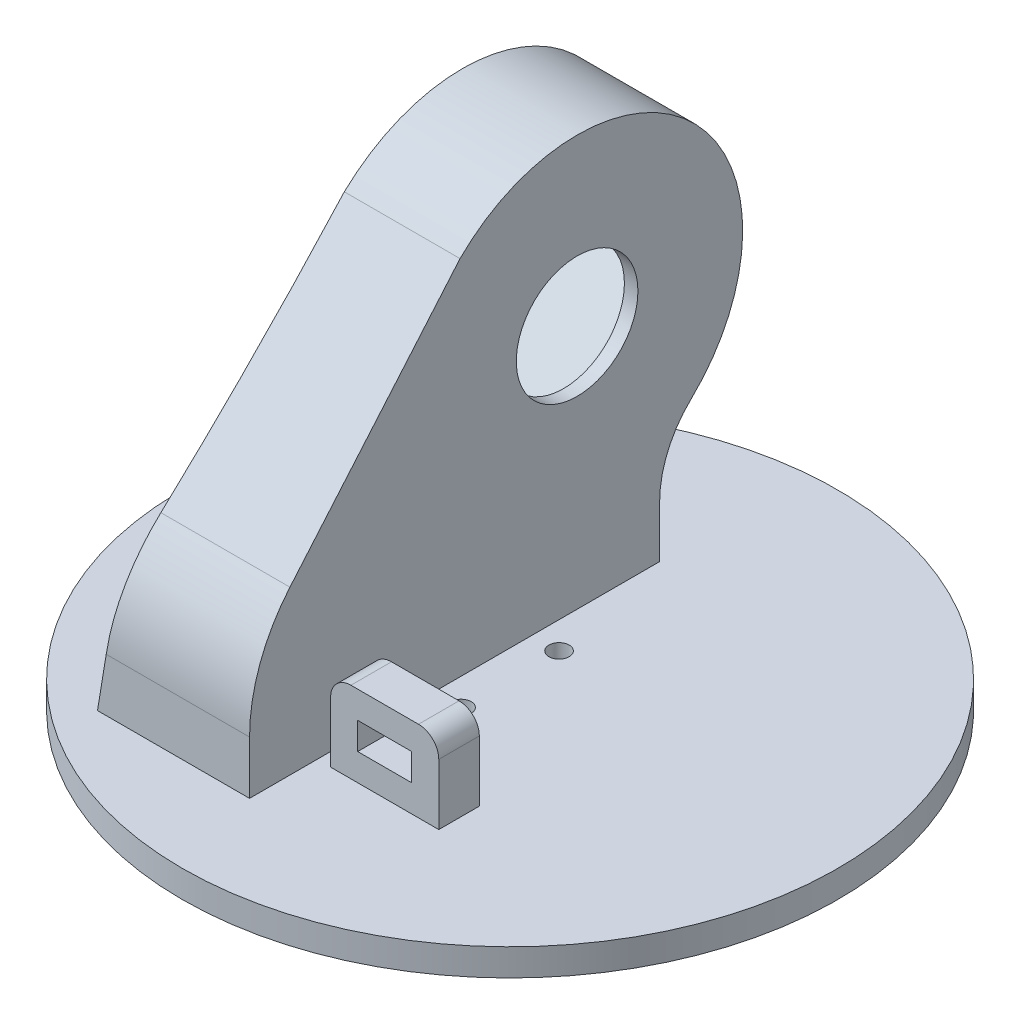
SolidWorks part; units mm, degrees
material "ABS"
ref_plane "Front Plane" through (0, 0, 0) normal (0, 0, 1) x (1, 0, 0)
ref_plane "Top Plane" through (0, 0, 0) normal (0, 1, 0) x (1, 0, 0)
ref_plane "Right Plane" through (0, 0, 0) normal (1, 0, 0) x (0, 0, -1)
sketch "Sketch2" plane through (0, 0, 0) normal (0, 1, 0) x (1, 0, 0)
  circle A0 centre (0, 0) radius 48.5
  dimension "D1" = 97
extrude "Boss-Extrude1" add sketch "Sketch2" along normal blind 4
sketch "Sketch4" plane through (0, 0, 0) normal (0, -1, 0) x (1, 0, 0)
  circle A0 centre (0, 7.25) radius 1.5
  circle A1 centre (0, -7.25) radius 1.5
  dimension "D1" = 3
  dimension "D2" = 3
  dimension "D3" = 14.5
  dimension "D4" = 7.25
extrude "Cut-Extrude2" cut sketch "Sketch4" against normal through all
sketch "Sketch5" plane through (0, 0, 0) normal (0, -1, 0) x (1, 0, 0)
  circle A0 centre (0, 0) radius 3.75
  dimension "D1" = 7.5
extrude "Cut-Extrude3" cut sketch "Sketch5" against normal blind 1.5
ref_plane "Plane1" through (-4, 0, 0) normal (1, 0, 0) x (0, 0, -1)
sketch "Sketch7" plane through (-4, 0, 0) normal (1, 0, 0) x (0, 0, -1)
  line L0 (23.1299, 11.6445) -> (23.1299, 4)
  line L5 (48.5, 4) -> (-48.5, 4) construction
  line L6 (-27.2273, 29.5362) -> (-1.2843, 55.4793)
  line L7 (-43.5609, 4) -> (23.1299, 4)
  line L11 (-34.5496, 4) -> (-34.5496, 11.8586)
  arc A4 (28.7298, 24.692) -> (-1.2843, 55.4793) centre (13.9185, 40.2765) ccw
  arc A5 (28.7298, 24.692) -> (23.1299, 11.6445) centre (41.1299, 11.6445) ccw
  arc A6 (-27.2273, 29.5362) -> (-34.5496, 11.8586) centre (-9.5496, 11.8586) ccw
  dimension "D1" = 25
  dimension "D4" = 43
  dimension "D3" = 18
  dimension "D5" = 45
extrude "Boss-Extrude2" add sketch "Sketch7" against normal blind 14 contours A5 A4 L6 L7 L0 | A4 | A4 | A4 | L6 A6 L7 region at (-4, 29.3392, -2.7362)
ref_plane "Plane2" through (-6, 0, 0) normal (1, 0, 0) x (0, 0, -1)
sketch "Sketch8" plane through (-6, 0, 0) normal (1, 0, 0) x (0, 0, -1)
  line L0 (-27.2273, 29.5362) -> (-1.2843, 55.4793) construction
  line L1 (-15.2496, 25.9576) -> (13.7417, 54.9489)
  line L2 (-15.2496, 25.9576) -> (-0.4004, 11.1083)
  line L3 (-0.4004, 11.1083) -> (28.591, 40.0997)
  line L4 (13.7417, 54.9489) -> (28.591, 40.0997)
  line L5 (-15.2496, 25.9576) -> (28.591, 40.0997) construction
  line L6 (-0.4004, 11.1083) -> (13.7417, 54.9489) construction
  point P0 (6.6707, 33.0286)
  point P11 (13.9185, 40.2765)
  dimension "D1" = 41
  dimension "D2" = 21
  dimension "D3" = 90
  dimension "D4" = 20.5
  dimension "D5" = 90
  dimension "D6" = 10.25
  dimension "D7" = 10.5
extrude "Cut-Extrude5" cut sketch "Sketch8" against normal up to next
sketch "Sketch9" plane through (-18, 0, 0) normal (-1, 0, 0) x (0, 0, 1)
  line L0 (-13.7417, 54.9489) -> (-28.591, 40.0997) construction
  line L3 (-21.1664, 47.5243) -> (-22.536, 48.894) construction
  circle A0 centre (-20.1057, 53.5347) radius 1.3
  circle A1 centre (-27.1768, 46.4637) radius 1.3
  circle A2 centre (6.7644, 12.5225) radius 1.3
  circle A3 centre (13.8354, 19.5936) radius 1.3
  dimension "D1" = 2.6
  dimension "D5" = 5
  dimension "D6" = 90
  dimension "D2" = 3.5
  dimension "D3" = 2
  dimension "D4" = 2
extrude "Cut-Extrude6" cut sketch "Sketch9" against normal blind 7.5
sketch "Sketch11" plane through (-4, 0, 0) normal (1, 0, 0) x (0, 0, -1)
  circle A0 centre (13.9185, 40.2765) radius 9
  dimension "D1" = 18
extrude "Cut-Extrude9" cut sketch "Sketch11" against normal up to next
sketch "Sketch17" plane through (-18, 0, 0) normal (-1, 0, 0) x (0, 0, 1)
  line L0 (29.3486, 31.6576) -> (3.4056, 57.6006)
  line L1 (-26.1299, 11.6445) -> (-26.1299, 1)
  line L2 (-26.1299, 1) -> (37.5496, 1)
  line L3 (37.5496, 1) -> (37.5496, 11.8586)
  line L4 (27.2273, 29.5362) -> (1.2843, 55.4793)
  line L5 (-23.1299, 11.6445) -> (-23.1299, 4)
  line L6 (-23.1299, 4) -> (34.5496, 4)
  line L7 (34.5496, 4) -> (34.5496, 11.8586)
  line L9 (-23.1299, 11.6445) -> (-23.1299, 4)
  line L10 (-23.1299, 4) -> (34.5496, 4)
  line L11 (34.5496, 4) -> (34.5496, 11.8586)
  line L12 (-26.1299, 4) -> (37.5496, 4)
  line L13 (48.5, 4) -> (-48.5, 4) construction
  line L14 (3.4056, 57.6006) -> (28.5745, 28.0776)
  line L15 (1.2843, 55.4793) -> (26.295, 26.1272)
  line L16 (31.5496, 11.8586) -> (31.5496, 4)
  line L18 (27.2273, 29.5362) -> (1.2843, 55.4793) construction
  arc A0 (3.4056, 57.6006) -> (-30.7965, 22.5174) centre (-13.9185, 40.2765) ccw
  arc A1 (-26.1299, 11.6445) -> (-30.7965, 22.5174) centre (-41.1299, 11.6445) ccw
  arc A2 (37.5496, 11.8586) -> (29.3486, 31.6576) centre (9.5496, 11.8586) ccw
  arc A3 (1.2843, 55.4793) -> (-28.7298, 24.692) centre (-13.9185, 40.2765) ccw
  arc A4 (-23.1299, 11.6445) -> (-28.7298, 24.692) centre (-41.1299, 11.6445) ccw
  arc A5 (34.5496, 11.8586) -> (27.2273, 29.5362) centre (9.5496, 11.8586) ccw
  arc A6 (1.2843, 55.4793) -> (-28.7298, 24.692) centre (-13.9185, 40.2765) ccw
  arc A7 (-23.1299, 11.6445) -> (-28.7298, 24.692) centre (-41.1299, 11.6445) ccw
  arc A8 (34.5496, 11.8586) -> (27.2273, 29.5362) centre (9.5496, 11.8586) ccw
  arc A9 (31.5496, 11.8586) -> (25.106, 27.4149) centre (9.5496, 11.8586) ccw
  line M16 (27.2273, 29.5362) -> (1.2843, 55.4793)
  arc M17 (1.2843, 55.4793) -> (-28.7298, 24.692) centre (-13.9185, 40.2765) ccw
  arc M18 (-28.7298, 24.692) -> (-23.1299, 11.6445) centre (-41.1299, 11.6445) cw
  line M19 (-23.1299, 11.6445) -> (-23.1299, 4)
  line M21 (34.5496, 4) -> (34.5496, 11.8586)
  arc M22 (34.5496, 11.8586) -> (27.2273, 29.5362) centre (9.5496, 11.8586) ccw
  dimension "D1" = 0
  dimension "D2" = 3
  dimension "D3" = 3
extrude "Boss-Extrude7" add sketch "Sketch17" along normal blind 9 and the other way up to surface (14 mm away) contours A9 L16 L12 L15 M21 M22 M16 | A1 L1 L12 L14 A0 M19 M18 M17 M16 M22 region at (-18, 42.2523, 15.3017) region at (-18, 20.289, 32.4332) other way up to face at (-4, 40.2765, -22.9185)
sketch "Sketch25" plane through (-18, 0, 0) normal (-1, 0, 0) x (0, 0, 1)
  line L0 (-23.1299, 11.6445) -> (-23.1299, 4)
  line L1 (48.5, 4) -> (-48.5, 4) construction
  line L2 (-23.1299, 11.6445) -> (-23.1299, 4) construction
  line L3 (1.2843, 55.4793) -> (26.295, 26.1272) construction
  line L4 (31.5496, 4) -> (-23.1299, 4) construction
  line L5 (31.5496, 11.8586) -> (31.5496, 4) construction
  line L6 (31.5496, 4) -> (-23.1299, 4)
  line L7 (31.5496, 11.8586) -> (31.5496, 4)
  line L8 (1.2843, 55.4793) -> (26.295, 26.1272)
  arc A0 (-23.1299, 11.6445) -> (-28.7298, 24.692) centre (-41.1299, 11.6445) ccw construction
  arc A1 (1.2843, 55.4793) -> (-28.7298, 24.692) centre (-13.9185, 40.2765) ccw construction
  arc A2 (-23.1299, 11.6445) -> (-28.7298, 24.692) centre (-41.1299, 11.6445) ccw
  arc A3 (31.5496, 11.8586) -> (26.295, 26.1272) centre (9.5496, 11.8586) ccw construction
  arc A4 (31.5496, 11.8586) -> (26.295, 26.1272) centre (9.5496, 11.8586) ccw
  spline S0 degree 3 poles (-28.7298, 24.692) (-21.9549, 18.2532) (-19.0941, 12.798) (-15.1299, 4) knots 0 0 0 0 1 1 1 1
  spline S1 degree 2 poles (11.7516, 43.195) (26.5513, 25.8264) (25.5496, 4) knots 0 0 0 1 1 1
  dimension "D2" = 8
  dimension "D1" = 6
extrude "Boss-Extrude10" add sketch "Sketch25" along normal up to surface (9 mm away) contours S0 L6 L0 A2 | A4 S1 A2 S0 L8 region at (-18, 9.918, -20.706) region at (-18, 17.2593, 26.6261) up to face at (-27, 22.2911, 0.3951)
sketch "Sketch26" plane through (0, 0, 0) normal (0, 0, 1) x (1, 0, 0)
  line L0 (-4, 64.7765) -> (-27, 64.7765) construction
  line L1 (-27, 4) -> (-4, 4) construction
  line L2 (-27, 4) -> (-27, 11.8586) construction
  line L3 (-26, 64.7765) -> (-27, 64.7765)
  line L4 (-27, 64.7765) -> (-27, 4)
  line L5 (-27, 4) -> (-23, 4)
  spline S0 degree 2 poles (-26, 64.7765) (-24.7724, 34.3751) (-23, 4) knots 0 0 0 1 1 1
  dimension "D1" = 1
  dimension "D2" = 4
  dimension "D3" = 2
extrude "Cut-Extrude15" [suppressed] cut sketch "Sketch26" against normal through all both and the other way through all contours L4 L5 S0 L3
sketch "Sketch27" plane through (0, 4, 0) normal (0, 1, 0) x (1, 0, 0)
  line L1 (-2, -18.5496) -> (14, -18.5496)
  line L2 (-2, -18.5496) -> (-2, -24.5496)
  line L3 (-2, -24.5496) -> (14, -24.5496)
  line L4 (14, -18.5496) -> (14, -24.5496)
  line L5 (-27, -34.5496) -> (-4, -34.5496) construction
  line L6 (-4, -34.5496) -> (-4, 26.1299) construction
  dimension "D1" = 10
  dimension "D2" = 6
  dimension "D3" = 16
  dimension "D4" = 2
extrude "Boss-Extrude11" add sketch "Sketch27" along normal blind 12
fillet "Fillet6" radius 3 2 edges at (14, 16, 21.5496) (-2, 16, 21.5496)
sketch "Sketch28" plane through (0, 0, 24.5496) normal (0, 0, 1) x (1, 0, 0)
  line L8 (10, 12) -> (2, 12)
  line L9 (2, 12) -> (2, 8)
  line L10 (2, 8) -> (10, 8)
  line L11 (10, 8) -> (10, 12)
  line L12 (10, 12) -> (2, 12)
  line L13 (2, 12) -> (2, 8)
  line L14 (2, 8) -> (10, 8)
  line L15 (10, 8) -> (10, 12)
  dimension "D1" = 4
extrude "Cut-Extrude16" cut sketch "Sketch28" against normal up to next
sketch "Sketch29" plane through (0, 0, 0) normal (0, 0, 1) x (1, 0, 0)
  line L0 (-4, 64.7765) -> (-27, 64.7765) construction
  line L1 (-27, 4) -> (-4, 4) construction
  line L2 (-21, 64.7765) -> (-27, 64.7765)
  line L3 (-27, 64.7765) -> (-27, 4)
  line L4 (-27, 4) -> (-26.5, 4)
  line L5 (48.5, 4) -> (-48.5, 4) construction
  spline S0 degree 2 poles (-21, 64.7765) (-21.2205, 34.1409) (-26.5, 4) knots 0 0 0 1 1 1
  dimension "D1" = 6
  dimension "D2" = 4
  dimension "D3" = 0.5
  dimension "D4" = 25
extrude "Cut-Extrude17" cut sketch "Sketch29" against normal through all both and the other way through all
